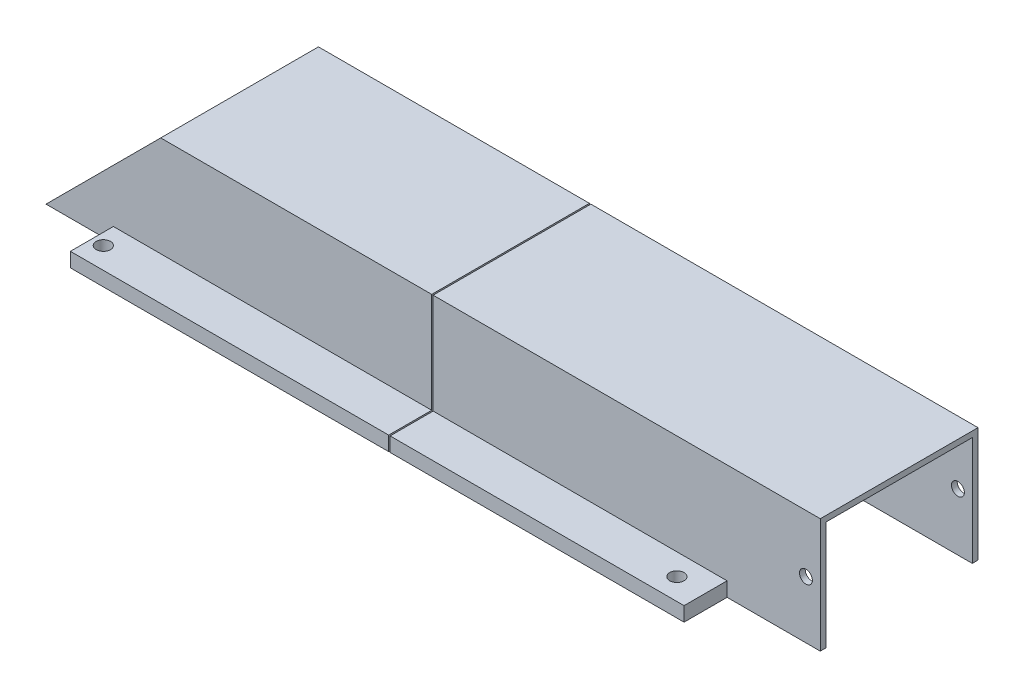
SolidWorks part; units mm, degrees
ref_plane "Front Plane" through (0, 0, 0) normal (0, 0, 1) x (1, 0, 0)
ref_plane "Top Plane" through (0, 0, 0) normal (0, 1, 0) x (1, 0, 0)
ref_plane "Right Plane" through (0, 0, 0) normal (1, 0, 0) x (0, 0, -1)
sketch "Sketch1" plane through (0, 0, 0) normal (0, 1, 0) x (1, 0, 0)
  line L0 (-127.5, 42.5) -> (-127.5, -42.5)
  line L1 (-125.5, -25.5) -> (125.5, -25.5)
  line L2 (-125.5, -25.5) -> (-125.5, 25.5)
  line L3 (-125.5, 25.5) -> (125.5, 25.5)
  line L4 (125.5, -25.5) -> (125.5, 25.5)
  line L5 (-125.5, -25.5) -> (125.5, 25.5) construction
  line L6 (-125.5, 25.5) -> (125.5, -25.5) construction
  line L7 (-142.5, -42.5) -> (142.5, -42.5)
  line L8 (-142.5, -42.5) -> (-142.5, 42.5)
  line L9 (-142.5, 42.5) -> (142.5, 42.5)
  line L10 (142.5, -42.5) -> (142.5, 42.5)
  line L11 (-142.5, -42.5) -> (142.5, 42.5) construction
  line L12 (-142.5, 42.5) -> (142.5, -42.5) construction
  point P0 (0, 0)
  point P6 (0, 0)
  dimension "D1" = 251
  dimension "D2" = 51
  dimension "D3" = 17
  dimension "D4" = 17
  dimension "D5" = 2
extrude "Boss-Extrude1" add sketch "Sketch1" along normal blind 5 contours L7 L10 L9 L0 L4 L1 L2 L3 region at (7.5, 0, -39.6694)
sketch "Sketch2" plane through (0, 5, 0) normal (0, 1, 0) x (1, 0, 0)
  line L0 (125.5, -25.5) -> (125.5, 25.5) construction
  line L1 (-125.5, -25.5) -> (125.5, -25.5) construction
  line L2 (-125.5, 25.5) -> (-125.5, -25.5) construction
  line L3 (125.5, 25.5) -> (-125.5, 25.5) construction
  line L4 (125.5, -25.5) -> (125.5, 25.5)
  line L5 (-125.5, -25.5) -> (125.5, -25.5)
  line L6 (-125.5, 25.5) -> (-125.5, -25.5)
  line L7 (125.5, 25.5) -> (-125.5, 25.5)
  line L8 (127.5, 27.5) -> (-127.5, 27.5)
  line L9 (-127.5, 27.5) -> (-127.5, -27.5)
  line L10 (-127.5, -27.5) -> (127.5, -27.5)
  line L11 (127.5, -27.5) -> (127.5, 27.5)
  line L12 (127.5, 27.5) -> (142.5, 27.5)
  line L13 (142.5, -42.5) -> (142.5, 42.5) construction
  line L14 (127.5, -27.5) -> (142.5, -27.5)
  line L15 (142.5, -27.5) -> (142.5, 27.5)
  line L16 (127.5, 27.5) -> (127.5, -27.5)
  dimension "D1" = 2
extrude "Boss-Extrude2" add sketch "Sketch2" along normal blind 35 contours L11 L14 L12 | L10 L11 L8 L9 region at (127.2391, 5, 0) region at (135, 5, 0)
sketch "Sketch3" plane through (0, 40, 0) normal (0, 1, 0) x (1, 0, 0)
  line L4 (142.5, 27.5) -> (-127.5, 27.5)
  line L5 (-127.5, 27.5) -> (-127.5, -27.5)
  line L6 (-127.5, -27.5) -> (142.5, -27.5)
  line L7 (142.5, -27.5) -> (142.5, 27.5)
  line L8 (142.5, 27.5) -> (-127.5, 27.5)
  line L9 (-127.5, 27.5) -> (-127.5, -27.5)
  line L10 (-127.5, -27.5) -> (142.5, -27.5)
  line L12 (142.5, -27.5) -> (142.5, 27.5)
  dimension "D1" = 0
extrude "Boss-Extrude3" add sketch "Sketch3" against normal blind 2
sketch "Sketch4" plane through (142.5, 0, 0) normal (1, 0, 0) x (0, 0, -1)
  line L0 (-42.5, 0) -> (42.5, 0) construction
  line L1 (-25.5, 0) -> (25.5, 0)
  line L2 (-25.5, 0) -> (-25.5, 38)
  line L3 (-25.5, 38) -> (25.5, 38)
  line L4 (25.5, 0) -> (25.5, 38)
  line L5 (-25.5, 0) -> (25.5, 38) construction
  line L6 (-25.5, 38) -> (25.5, 0) construction
  line L7 (-27.5, 40) -> (27.5, 40) construction
  line L8 (27.5, 40) -> (27.5, 5) construction
  point P0 (0, 19)
  dimension "D1" = 2
  dimension "D2" = 2
extrude "Cut-Extrude1" cut sketch "Sketch4" against normal blind 17
hole_wizard "CBORE for M5 Hex Head Bolt1" positions "Sketch5" profile "Sketch7" counterbore size "M5" standard "ANSI Metric" end condition through all
sketch "Sketch5" plane through (0, 5, 0) normal (0, 1, 0) x (1, 0, 0)
  line L1 (-100, -35) -> (100, -35)
  line L2 (-100, -35) -> (-100, 35)
  line L3 (-100, 35) -> (100, 35)
  line L4 (100, -35) -> (100, 35)
  line L5 (-100, -35) -> (100, 35) construction
  line L6 (-100, 35) -> (100, -35) construction
  point P2 (100, 35)
  point P139 (-100, -35)
  point P140 (-100, 35)
  point P141 (100, -35)
  dimension "D1" = 70
  dimension "D2" = 200
sketch "Sketch7" plane through (100, 5, -35) normal (1, 0, 0) x (0, 0, 1)
  line L0 (0, 0) -> (0, 5)
  line L1 (0, 5) -> (2.25, 5)
  line L3 (2.25, 5) -> (2.25, 4.2)
  line L4 (2.25, 4.2) -> (2.5, 4.2)
  line L5 (2.5, 4.2) -> (2.5, 0)
  line L7 (2.5, 0) -> (0, 0)
  line L11 (0, -6.35) -> (0, 107.95) construction
  dimension "Thru Hole Dia." = 4.5
  dimension "Thru Hole Depth" = 5
  dimension "C'Bore Dia." = 5
  dimension "C'Bore Depth" = 4.2
sketch "Sketch8" plane through (0, 5, 0) normal (0, 1, 0) x (1, 0, 0)
  line L0 (110, 42.5) -> (110, -42.5)
  line L8 (-127.5, -27.5) -> (-127.5, 27.5)
  line L9 (-127.5, 27.5) -> (142.5, 27.5)
  line L10 (142.5, 27.5) -> (142.5, 42.5)
  line L11 (142.5, 42.5) -> (-142.5, 42.5)
  line L12 (-142.5, 42.5) -> (-142.5, -42.5)
  line L13 (-142.5, -42.5) -> (142.5, -42.5)
  line L14 (142.5, -42.5) -> (142.5, -27.5)
  line L15 (142.5, -27.5) -> (-127.5, -27.5)
  line L16 (-127.5, -27.5) -> (-127.5, 27.5)
  line L17 (-127.5, 27.5) -> (142.5, 27.5)
  line L18 (142.5, 27.5) -> (142.5, 42.5)
  line L19 (142.5, 42.5) -> (-142.5, 42.5)
  line L20 (-142.5, 42.5) -> (-142.5, -42.5)
  line L21 (-142.5, -42.5) -> (142.5, -42.5)
  line L22 (142.5, -42.5) -> (142.5, -27.5)
  line L23 (142.5, -27.5) -> (-127.5, -27.5)
  circle A0 centre (100, 35) radius 1.65 construction
  dimension "D2" = 10
  dimension "D1" = 0
extrude "Cut-Extrude2" cut sketch "Sketch8" against normal blind 10 contours L0 | L0 region at (126.25, 5, -35) region at (126.25, 5, 35)
sketch "Sketch9" plane through (0, 5, 0) normal (0, 1, 0) x (1, 0, 0)
  line L0 (-127.5, 27.5) -> (110, 27.5) construction
  line L9 (-142.5, 42.5) -> (-104, 42.5)
  line L10 (-142.5, 42.5) -> (-142.5, 27.5)
  line L11 (-142.5, 27.5) -> (-104, 27.5)
  line L12 (-104, 42.5) -> (-104, 27.5)
  circle A0 centre (-100, 35) radius 1.65 construction
  dimension "D1" = 4
extrude "Cut-Extrude3" cut sketch "Sketch9" against normal blind 10
mirror "Mirror1" about plane through (0, 0, 0) normal (0, 0, 1) of "Cut-Extrude3"
hole_wizard "M4 Clearance Hole1" positions "Sketch11" profile "Sketch12" hole size "M4" standard "ANSI Metric" end condition through all
sketch "Sketch11" plane through (0, 0, 25.5) normal (0, 0, -1) x (-1, 0, 0)
  line L0 (-142.5, 40) -> (-142.5, 0) construction
  line L2 (127.5, 40) -> (-142.5, 40) construction
  point P0 (-137.5, 20)
  dimension "D1" = 5
  dimension "D2" = 20
sketch "Sketch12" plane through (137.5, 20, 25.5) normal (1, 0, 0) x (0, 1, 0)
  line L0 (0, 0) -> (0, 17)
  line L1 (0, 17) -> (2.25, 17)
  line L2 (2.25, 17) -> (2.25, 0)
  line L5 (2.25, 0) -> (0, 0)
  line L11 (0, -6.35) -> (0, 107.95) construction
  dimension "Thru Hole Dia." = 4.5
  dimension "Thru Hole Depth" = 17
mirror "Mirror2" about plane through (0, 0, 0) normal (0, 0, 1) of "M4 Clearance Hole1"
chamfer "Chamfer1" distance 40 angle 45 2 edges at (-127.5, 40, 0) (-125.5, 38, 0)
ref_plane "Plane1" through (7.5, 0, 0) normal (1, 0, 0) x (0, 0, -1)
sketch "Sketch13" plane through (7.5, 0, 0) normal (1, 0, 0) x (0, 0, -1)
  line L1 (-46.5988, -49.8418) -> (46.5988, -49.8418)
  line L2 (-46.5988, -49.8418) -> (-46.5988, 49.8418)
  line L3 (-46.5988, 49.8418) -> (46.5988, 49.8418)
  line L4 (46.5988, -49.8418) -> (46.5988, 49.8418)
  line L5 (-46.5988, -49.8418) -> (46.5988, 49.8418) construction
  line L6 (-46.5988, 49.8418) -> (46.5988, -49.8418) construction
  point P0 (0, 0)
extrude "Cut-Extrude4" cut sketch "Sketch13" against normal blind 0.5
